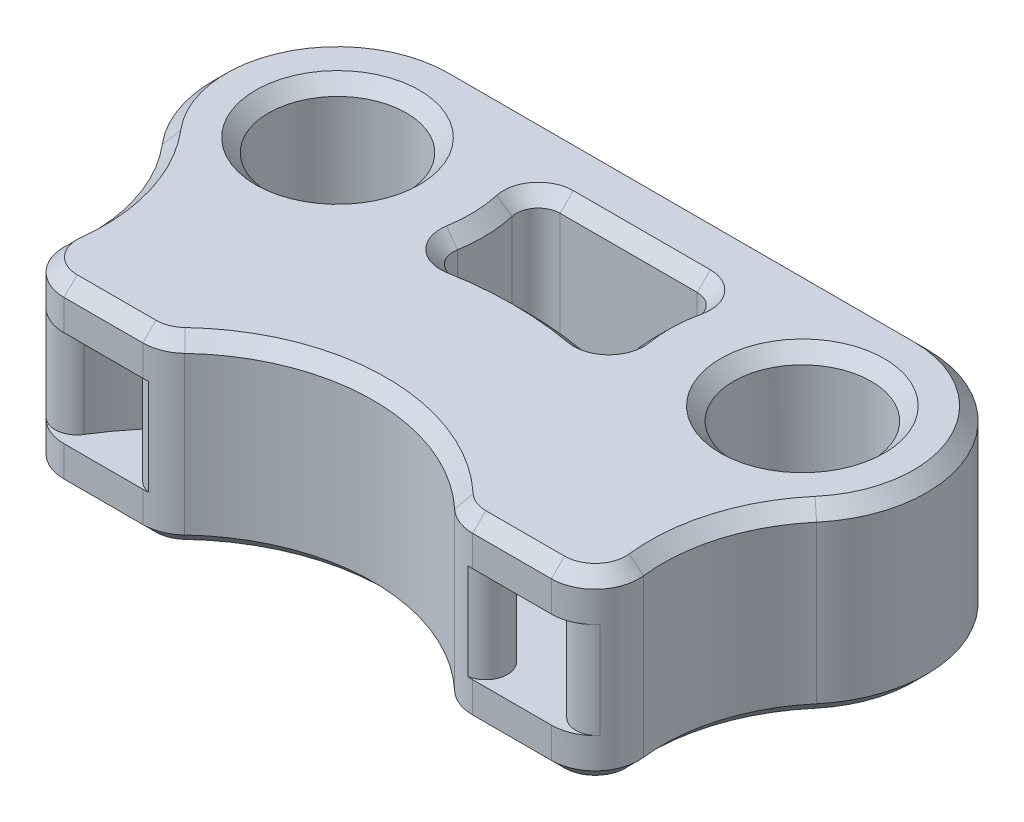
SolidWorks part; units mm, degrees
note: The reader was unsure of these and kept them because the rebuilt part matched: shared geometry of "Sketch1<4>", "Sketch1<5>".
ref_plane "Front Plane" through (0, 0, 0) normal (0, 0, 1) x (1, 0, 0)
ref_plane "Top Plane" through (0, 0, 0) normal (0, 1, 0) x (1, 0, 0)
ref_plane "Right Plane" through (0, 0, 0) normal (1, 0, 0) x (0, 0, -1)
sketch "Sketch1" plane through (0, 0, 0) normal (0, 1, 0) x (1, 0, 0)
  line L0 (-5.32, 0) -> (5.32, 0) construction
  line L1 (-6.8739, -6) -> (6.8739, -6)
  line L2 (0, -9) -> (0, 0) construction
  line L3 (-5.32, 2.845) -> (5.32, 2.845)
  line L4 (-5.32, 1.845) -> (5.32, 1.845)
  line L5 (-5.32, 1.345) -> (5.32, 1.345)
  circle A0 centre (-5.32, 0) radius 1.575
  circle A1 centre (5.32, 0) radius 1.575
  circle A2 centre (0, -9) radius 4.5
  circle A3 centre (0, -9) radius 5.5
  circle A4 centre (0, -9) radius 7.5
  circle A5 centre (5.32, 0) radius 2.845
  circle A6 centre (-5.32, 0) radius 2.845
  arc A7 (-6.8739, -6) -> (-7.4875, -1.8428) centre (-10.5104, -4.4129) ccw
  circle A8 centre (0, -9) radius 8
  arc A9 (6.8739, -6) -> (7.4875, -1.8428) centre (10.5104, -4.4129) cw
  circle A10 centre (0, -9) radius 6.5
  circle A11 centre (5.32, 0) radius 3.345
  circle A12 centre (-5.32, 0) radius 3.345
  point P6 (0, 0)
  dimension "D1" = 9
  dimension "D2" = 3.15
  dimension "D10" = 1
  dimension "D3" = 10.64
  dimension "D4" = 9
  dimension "D9" = 3
  dimension "D5" = 1
  dimension "D6" = 2
  dimension "D7" = 1.27
  dimension "D8" = 1.27
  dimension "D11" = 1
  dimension "D12" = 0.5
  dimension "D13" = 0.5
extrude "Boss-Extrude1" add sketch "Sketch1" along normal blind 4.2
extrude "Cut-Extrude1" cut sketch "Sketch1<4>" along normal blind 2.2 from offset 1 contours L1 A10 A3
sketch "Sketch1<4>" plane through (0, 0, 0) normal (0, 1, 0) x (1, 0, 0) same geometry as "Sketch1"
fillet "Fillet1" radius 1 2 edges at (6.8739, 2.1, 6) (-6.8739, 2.1, 6)
fillet "Fillet2" radius 0.5 2 edges at (-4.6098, 2.1, 6) (4.6098, 2.1, 6)
fillet "Fillet7" radius 0.5 2 edges at (-5.7577, 2.1, 5.9836) (5.7577, 2.1, 5.9836)
fillet "Fillet8" radius 1 2 edges at (3.3541, 2.1, 6) (-3.3541, 2.1, 6)
extrude "Cut-Extrude2" cut sketch "Sketch1<5>" along normal through all
sketch "Sketch1<5>" plane through (0, 0, 0) normal (0, 1, 0) x (1, 0, 0) same geometry as "Sketch1"
fillet "Fillet9" radius 0.5 4 edges at (2.2474, 2.1, 1.3222) (2.2573, 2.1, -1.345) (-2.2573, 2.1, -1.345) (-2.2474, 2.1, 1.3222)
chamfer "Chamfer1" distance 0.3 angle 45 44 edges at (5.32, 0, 1.575) (1.9595, 0, -1.1573) (1.9763, 0, -0.0915) (1.8795, 0, 0.9946) (0, 0, 1) (-1.8795, 0, 0.9946) (-1.9763, 0, -0.0915) (-1.9595, 0, -1.1573) (0, 0, -1.345) (-5.32, 0, 1.575) (-6.7118, 0, 3.2666) (-6.3252, 0, 5.664) (-4.6762, 0, 6) (-3.4056, 0, 5.9293) (0, 0, 4.5) (3.4056, 0, 5.9293) (4.6762, 0, 6) (6.3252, 0, 5.664) (6.7118, 0, 3.2666) (7.9023, 0, -1.194) (0, 0, -2.845) (-7.9023, 0, -1.194) (5.32, 4.2, 1.575) (1.9595, 4.2, -1.1573) (0, 4.2, -1.345) (-1.9595, 4.2, -1.1573) (-1.9763, 4.2, -0.0915) (-1.8795, 4.2, 0.9946) (0, 4.2, 1) (1.8795, 4.2, 0.9946) (1.9763, 4.2, -0.0915) (-5.32, 4.2, 1.575) (7.9023, 4.2, -1.194) (6.7118, 4.2, 3.2666) (6.3252, 4.2, 5.664) (4.6762, 4.2, 6) (3.4056, 4.2, 5.9293) (0, 4.2, 4.5) (-3.4056, 4.2, 5.9293) (-4.6762, 4.2, 6) (-6.3252, 4.2, 5.664) (-6.7118, 4.2, 3.2666) (-7.9023, 4.2, -1.194) (0, 4.2, -2.845)
